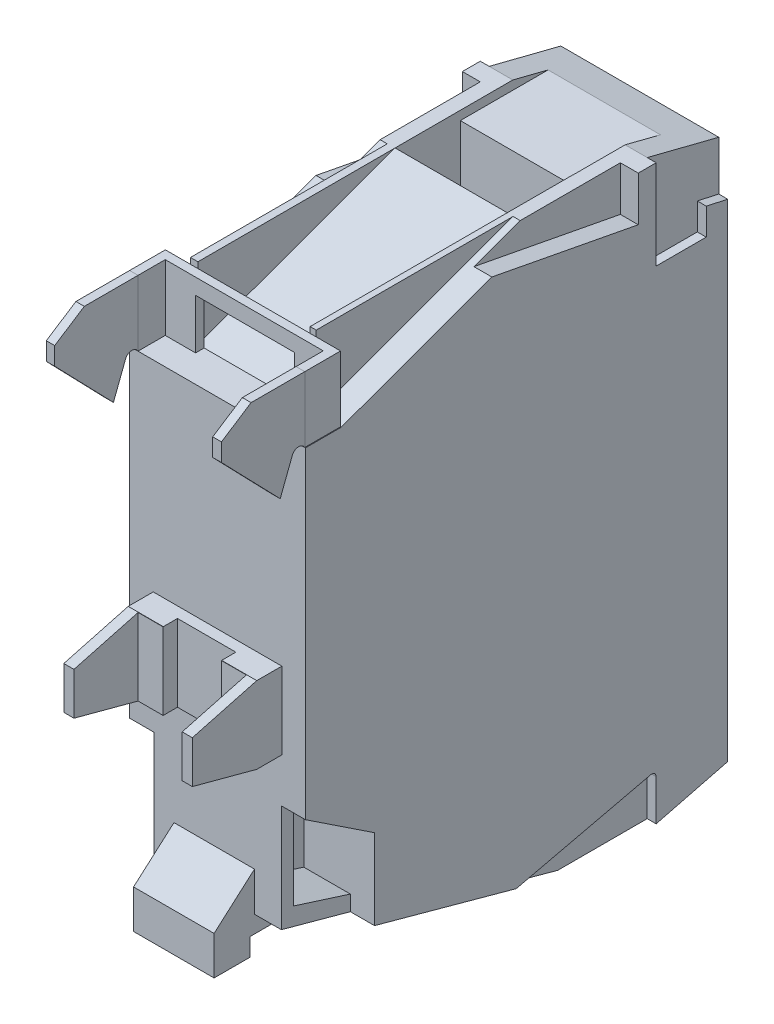
SolidWorks part; units mm, degrees
ref_plane "Front Plane" through (0, 0, 0) normal (0, 0, 1) x (1, 0, 0)
ref_plane "Top Plane" through (0, 0, 0) normal (0, 1, 0) x (1, 0, 0)
ref_plane "Right Plane" through (0, 0, 0) normal (1, 0, 0) x (0, 0, -1)
sketch "Sketch1" plane through (0, 0, 0) normal (0, 0, 1) x (1, 0, 0)
  line L0 (-4.915, -16) -> (4.915, 16) construction
  line L1 (-4.915, 16) -> (4.915, 16)
  line L2 (-4.915, 16) -> (-4.915, -16)
  line L3 (-4.915, -16) -> (4.915, -16)
  line L4 (4.915, 16) -> (4.915, -16)
  line L5 (0, 16) -> (0, -16) construction
  point P4 (0, 0)
  dimension "D1" = 9.83
  dimension "D2" = 32
extrude "Boss-Extrude1" add sketch "Sketch1" along normal blind 23.6
sketch "Sketch2" plane through (4.915, 0, 0) normal (1, 0, 0) x (0, 0, -1)
  line L0 (0, 14.9858) -> (-4, 14.9858) construction
  line L1 (0, -16) -> (0, 16) construction
  line L2 (-4, 16) -> (-4, 15) construction
  line L3 (-23.6, 16) -> (0, 16) construction
  line L4 (-4, 16) -> (0, 14.9858)
  line L5 (-4, 16) -> (0, 16)
  line L6 (0, 16) -> (0, 14.9858)
  line L7 (-23.6, 0) -> (0, 0) construction
  line L8 (-23.6, -16) -> (-23.6, 16) construction
  line L9 (-4, -16) -> (-4, -15) construction
  line L10 (0, -14.9858) -> (-4, -14.9858) construction
  line L11 (0, -16) -> (0, -14.9858)
  line L12 (-4, -16) -> (0, -16)
  line L13 (-4, -16) -> (0, -14.9858)
extrude "Cut-Extrude1" cut sketch "Sketch2" against normal up to next
sketch "Sketch3" plane through (4.915, 0, 0) normal (1, 0, 0) x (0, 0, -1)
  line L0 (-4, 16) -> (-4, 11)
  line L1 (-4, 11) -> (-1.2, 11)
  line L2 (-1.2, 11) -> (-1.2, 12.5)
  line L3 (-1.2, 12.5) -> (0, 12.2359)
  line L4 (0, -14.9858) -> (0, 14.9858) construction
  line L5 (0, 12.2359) -> (0, 14.9858)
  line L6 (0, 14.9858) -> (-4, 16)
sketch "Sketch5" plane through (-4.915, 0, 0) normal (-1, 0, 0) x (0, 0, 1)
  line L0 (4, 16) -> (4, 11)
  line L1 (4, 11) -> (1.2, 11)
  line L2 (1.2, 11) -> (1.2, 12.5)
  line L3 (1.2, 12.5) -> (0, 12.2359)
  line L4 (0, 12.2359) -> (0, 14.9858)
  line L5 (0, 14.9858) -> (4, 16)
extrude "Cut-Extrude2" cut sketch "Sketch5" against normal blind 0.5
extrude "Cut-Extrude3" cut sketch "Sketch3" against normal blind 0.5
sketch "Sketch6" plane through (4.915, 0, 0) normal (1, 0, 0) x (0, 0, -1)
  line L0 (-4, -16) -> (-9, -16) construction
  line L1 (-23.6, -16) -> (-4, -16) construction
  line L2 (-23.6, 16) -> (-23.6, -12) construction
  line L3 (-23.6, -16) -> (-23.6, 16) construction
  line L4 (-23.6, -12) -> (-9, -16)
  line L5 (-9, -16) -> (-23.6, -16)
  line L6 (-23.6, -16) -> (-23.6, -12)
extrude "Cut-Extrude4" cut sketch "Sketch6" against normal up to next
sketch "Sketch7" plane through (4.915, 0, 0) normal (1, 0, 0) x (0, 0, -1)
  line L0 (-23.6, 2) -> (0, 2) construction
  line L1 (-23.6, -12) -> (-23.6, 16) construction
  line L2 (0, -14.9858) -> (0, 12.2359) construction
  line L3 (-4, -16) -> (-4, -13.7152)
  line L4 (-4.3069, -13.4717) -> (-11.8196, -15.2275)
  line L5 (-9, -16) -> (-23.6, -12) construction
  line L6 (-11.8196, -15.2275) -> (-9, -16)
  line L7 (-9, -16) -> (-4, -16)
  arc A0 (-4, -13.7152) -> (-4.3069, -13.4717) centre (-4.25, -13.7152) ccw
  dimension "D1" = 0.25
extrude "Cut-Extrude5" cut sketch "Sketch7" against normal blind 0.5
sketch "Sketch8" plane through (-4.915, 0, 0) normal (-1, 0, 0) x (0, 0, 1)
  line L0 (4, -16) -> (4, -13.7152)
  line L1 (4, -13.7152) -> (4.0946, -13.5193)
  line L2 (4.0946, -13.5193) -> (4.3069, -13.4717)
  line L3 (4.3069, -13.4717) -> (11.8196, -15.2275)
  line L4 (11.8196, -15.2275) -> (9, -16)
  line L5 (9, -16) -> (4, -16)
  arc A0 (4.3069, -13.4717) -> (4, -13.7152) centre (4.25, -13.7152) ccw construction
extrude "Cut-Extrude6" cut sketch "Sketch8" against normal blind 0.5 contours L5 L0 L1 L2 L3 L4
sketch "Sketch9" plane through (4.915, 0, 0) normal (1, 0, 0) x (0, 0, -1)
  line L1 (-23.6, 16) -> (-21.6, 16)
  line L2 (-23.6, 16) -> (-23.6, 12)
  line L3 (-23.6, 12) -> (-21.6, 12)
  line L4 (-21.6, 16) -> (-21.6, 12)
extrude "Cut-Extrude7" cut sketch "Sketch9" against normal up to next
sketch "Sketch10" plane through (4.915, 0, 0) normal (1, 0, 0) x (0, 0, -1)
  line L0 (-5, 13.5) -> (-4, 13.5) construction
  line L1 (-4, 16) -> (-4, 11) construction
  line L2 (-5, 13.5) -> (-5, 16)
  line L3 (-21.6, 16) -> (-4, 16) construction
  line L4 (-5, 13.5) -> (-18.1024, 16)
  line L5 (-18.1024, 16) -> (-5, 16)
extrude "Cut-Extrude8" cut sketch "Sketch10" against normal blind 1
sketch "Sketch11" plane through (4.915, 0, 0) normal (1, 0, 0) x (0, 0, -1)
  line L0 (-21.6, 16) -> (-10.6, 16)
  line L1 (-10.6, 16) -> (-21.6, 12)
  line L2 (-21.6, 12) -> (-21.6, 16)
extrude "Cut-Extrude9" cut sketch "Sketch11" against normal blind 1.4
sketch "Sketch12" plane through (-4.915, 0, 0) normal (-1, 0, 0) x (0, 0, 1)
  line L0 (5, 16) -> (5, 13.5)
  line L1 (5, 13.5) -> (18.1024, 16)
  line L2 (18.1024, 16) -> (5, 16)
extrude "Cut-Extrude10" cut sketch "Sketch12" against normal blind 1 contours L2 L0 L1
sketch "Sketch13" plane through (-4.915, 0, 0) normal (-1, 0, 0) x (0, 0, 1)
  line L0 (21.6, 12) -> (21.6, 16)
  line L1 (21.6, 16) -> (10.6, 16)
  line L2 (10.6, 16) -> (21.6, 12)
extrude "Cut-Extrude11" cut sketch "Sketch13" against normal blind 1.4
sketch "Sketch14" plane through (4.915, 0, 0) normal (1, 0, 0) x (0, 0, -1)
  line L0 (-23.6, -12) -> (-23.6, -6)
  line L1 (-23.6, -12) -> (-23.6, 12) construction
  line L2 (-23.6, -12) -> (-19.7422, -13.0569)
  line L3 (-11.8196, -15.2275) -> (-23.6, -12) construction
  line L4 (-19.7422, -13.0569) -> (-19.7422, -8.5569)
  line L5 (-19.7422, -8.5569) -> (-23.6, -6)
extrude "Cut-Extrude12" cut sketch "Sketch14" against normal blind 1.35
sketch "Sketch15" plane through (-4.915, 0, 0) normal (-1, 0, 0) x (0, 0, 1)
  line L0 (19.7422, -13.0569) -> (19.7422, -8.5569)
  line L1 (19.7422, -8.5569) -> (23.6, -6)
  line L2 (23.6, -6) -> (23.6, -12)
  line L3 (23.6, -12) -> (19.7422, -13.0569)
extrude "Cut-Extrude13" cut sketch "Sketch15" against normal blind 1.35
sketch "Sketch16" plane through (3.565, 0, 0) normal (1, 0, 0) x (0, 0, -1)
  line L0 (-22.9226, -6.449) -> (-22.9226, -11.1904)
  line L1 (-19.7422, -8.5569) -> (-23.6, -6) construction
  line L2 (-22.9226, -11.1904) -> (-19.7422, -12.2011)
  line L3 (-19.7422, -13.0569) -> (-19.7422, -8.5569) construction
  line L4 (-22.9226, -6.449) -> (-19.7422, -8.5569)
  line L5 (-19.7422, -8.5569) -> (-19.7422, -12.2011)
extrude "Cut-Extrude14" cut sketch "Sketch16" against normal blind 2.6
sketch "Sketch18" plane through (-3.565, 0, 0) normal (-1, 0, 0) x (0, 0, 1)
  line L0 (19.7422, -12.2011) -> (19.7422, -8.5569)
  line L1 (19.7422, -8.5569) -> (22.9226, -6.449)
  line L2 (22.9226, -6.449) -> (22.9226, -11.1904)
  line L3 (22.9226, -11.1904) -> (19.7422, -12.2011)
extrude "Cut-Extrude15" cut sketch "Sketch18" against normal blind 3.6
sketch "Sketch19" plane through (0, -14.0807, -3.5701) normal (0, -0.9693, -0.2458) x (1, 0, 0)
  line L1 (3.7246, 7.1036) -> (-3.4583, 7.1036)
  line L2 (3.7246, 7.1036) -> (3.7246, 4.9248)
  line L3 (3.7246, 4.9248) -> (-3.4583, 4.9248)
  line L4 (-3.4583, 7.1036) -> (-3.4583, 4.9248)
extrude "Cut-Extrude18" cut sketch "Sketch19" against normal blind 1.32
chamfer "Chamfer2" distance 0.75 angle 75 3 edges at (-3.4583, -15.5588, 2.2597) (0.1332, -15.291, 1.2037) (3.7246, -15.5588, 2.2597)
sketch "Sketch21" plane through (0, -14.0807, -3.5701) normal (0, -0.9693, -0.2458) x (-1, 0, 0)
  line L1 (-4.0773, -7.1036) -> (4.2083, -7.1036)
  line L2 (-4.0773, -7.1036) -> (-4.0773, -12.5673)
  line L3 (-4.0773, -12.5673) -> (4.2083, -12.5673)
  line L4 (4.2083, -7.1036) -> (4.2083, -12.5673)
extrude "Cut-Extrude19" cut sketch "Sketch21" against normal blind 4.25
sketch3d "3DSketch1" plane through (0, 0, 0) normal (0, 0, 1) x (1, 0, 0)
  dimension "D1" = 3.75
sketch "Sketch22" plane through (-0.185, 0, 0) normal (1, 0, 0) x (0, 0, -1)
  line L0 (-19.8581, -12.9572) -> (-23.8581, -12.9572)
  line L1 (-23.8581, -12.9572) -> (-23.8581, -13.9572)
  line L2 (-23.8581, -13.9572) -> (-25.8581, -13.9572)
  line L3 (-25.8581, -13.9572) -> (-25.8581, -11.7988)
  line L4 (-25.8581, -11.7988) -> (-23.5927, -9.8081)
  line L5 (-23.5927, -9.8081) -> (-23.4731, -11.3744)
  line L6 (-23.4731, -11.3744) -> (-19.8581, -12.9572)
extrude "Boss-Extrude2" add sketch "Sketch22" against normal blind 2.25 and the other way blind 2.25
sketch "Sketch23" plane through (0, 16, 0) normal (0, 1, 0) x (1, 0, 0)
  line L1 (-3.0982, -6.933) -> (3.1743, -6.933)
  line L2 (-3.0982, -6.933) -> (-3.0982, -21.6)
  line L3 (-3.0982, -21.6) -> (3.1743, -21.6)
  line L4 (3.1743, -6.933) -> (3.1743, -21.6)
  line L5 (-3.515, -21.6) -> (3.515, -21.6) construction
extrude "Cut-Extrude20" cut sketch "Sketch23" against normal up to vertex (4 mm away)
sketch "Sketch24" plane through (3.1743, 0, 0) normal (-1, 0, 0) x (0, 0, 1)
  line L0 (10.5797, 16) -> (21.6, 12)
  line L1 (21.6, 16) -> (6.933, 16) construction
  line L2 (21.6, 12) -> (10.5797, 12)
  line L3 (21.6, 12) -> (6.933, 12) construction
  line L4 (10.5797, 12) -> (10.5797, 16)
extrude "Boss-Extrude3" add sketch "Sketch24" along normal up to next
sketch "Sketch25" plane through (0, 16, 0) normal (0, 1, 0) x (1, 0, 0)
  line L1 (-3.0982, -6.933) -> (3.1814, -6.933)
  line L2 (-3.0982, -6.933) -> (-3.0982, -0.7769)
  line L3 (-3.0982, -0.7769) -> (3.1814, -0.7769)
  line L4 (3.1814, -6.933) -> (3.1814, -0.7769)
extrude "Cut-Extrude21" cut sketch "Sketch25" against normal blind 0.5
sketch "Sketch26" plane through (0, 0, 0) normal (0, 0, -1) x (-1, 0, 0)
  line L0 (-4.915, -1.375) -> (4.915, -1.375) construction
  line L3 (-3.5929, -3.5227) -> (3.5929, 0.7728) construction
  line L4 (-3.5929, 0.7728) -> (3.5929, 0.7728)
  line L5 (-3.5929, 0.7728) -> (-3.5929, -3.5227)
  line L6 (-3.5929, -3.5227) -> (3.5929, -3.5227)
  line L7 (3.5929, 0.7728) -> (3.5929, -3.5227)
  line L8 (4.915, 12.2359) -> (4.915, -14.9858) construction
  line L9 (-4.915, -14.9858) -> (-4.915, 12.2359) construction
  point P10 (0, -1.375)
  point P11 (0, -1.375)
  dimension "D1" = 7.1858
extrude "Cut-Extrude22" cut sketch "Sketch26" against normal through all
sketch "Sketch27" plane through (0, 0, 23.6) normal (0, 0, 1) x (1, 0, 0)
  line L1 (-3.5929, 0.7728) -> (3.5929, 0.7728)
  line L2 (-3.5929, 0.7728) -> (-3.5929, -3.5227)
  line L3 (-3.5929, -3.5227) -> (3.5929, -3.5227)
  line L4 (3.5929, 0.7728) -> (3.5929, -3.5227)
extrude "Boss-Extrude4" add sketch "Sketch27" along normal blind 5 and the other way blind 19.5 separate body
sketch "Sketch28" plane through (0, 0.7728, 0) normal (0, 1, 0) x (1, 0, 0)
  line L0 (3.0249, -28.6) -> (3.0249, -25.0138)
  line L1 (3.5929, -28.6) -> (-3.5929, -28.6) construction
  line L2 (3.0249, -25.0138) -> (1.6314, -25.0138)
  line L3 (1.6314, -25.0138) -> (1.6314, -24.2085)
  line L4 (1.6314, -24.2085) -> (-1.6314, -24.2085)
  line L5 (0, -24.2085) -> (0, -23.6)
  line L6 (3.5929, -23.6) -> (-3.5929, -23.6) construction
  line L7 (-3.5929, -23.6) -> (3.5929, -23.6)
  line L8 (3.5929, -23.6) -> (3.5929, -28.6)
  line L9 (3.5929, -28.6) -> (3.0249, -28.6)
  line L10 (0, -23.6) -> (0, -28.6) construction
  line L11 (-3.5929, -28.6) -> (-3.0249, -28.6)
  line L12 (-3.5929, -23.6) -> (-3.5929, -28.6)
  line L13 (-1.6314, -25.0138) -> (-1.6314, -24.2085)
  line L14 (-3.0249, -25.0138) -> (-1.6314, -25.0138)
  line L15 (-3.0249, -28.6) -> (-3.0249, -25.0138)
  line M11 (-3.5929, -28.6) -> (3.5929, -28.6)
extrude "Cut-Extrude23" cut sketch "Sketch28" against normal up to next (4.2956 mm away) contours L10 L4 L13 L14 L15 M11 | L4 L10 L0 L2 L3 M11
chamfer "Chamfer3" distance 3.6 angle 15 2 edges at (3.3089, 0.7728, 28.6) (3.3089, -3.5227, 28.6)
chamfer "Chamfer4" distance 3.6 angle 15 2 edges at (-3.3089, 0.7728, 28.6) (-3.3089, -3.5227, 28.6)
sketch "Sketch29" plane through (0, 0, 4.1) normal (0, 0, -1) x (-1, 0, 0)
  line L0 (3.5929, -3.5227) -> (-3.5929, -3.5227) construction
  line L1 (-1.7574, 0.6607) -> (1.7416, 0.6607)
  line L2 (-1.7574, 0.6607) -> (-1.7574, -3.5227)
  line L3 (-1.7574, -3.5227) -> (1.7416, -3.5227)
  line L4 (1.7416, 0.6607) -> (1.7416, -3.5227)
extrude "Boss-Extrude5" add sketch "Sketch29" along normal blind 0.25
sketch "Sketch30" plane through (0, 0, 0) normal (0, 0, -1) x (-1, 0, 0)
  line L1 (-4.3873, 11.3819) -> (4.2265, 11.3819)
  line L2 (-4.3873, 11.3819) -> (-4.3873, 7.8691)
  line L3 (-4.3873, 7.8691) -> (4.2265, 7.8691)
  line L4 (4.2265, 11.3819) -> (4.2265, 7.8691)
  circle A0 centre (0, 9.6814) radius 2.75
  circle A1 centre (0, -10.2363) radius 2.75
extrude "Cut-Extrude24" cut sketch "Sketch30" against normal blind 4 contours A0 L3 L4 L1 | L1 A0 L3 | L1 A0 | A1
sketch "Sketch31" plane through (0, 0, 4) normal (0, 0, -1) x (-1, 0, 0)
  line L0 (0, 12.4314) -> (0, 6.9314) construction
  line L1 (0, -10.2363) -> (0, -7.4863) construction
  arc A1 (2.1613, 11.3819) -> (-2.1613, 11.3819) centre (0, 9.6814) ccw construction
  arc A2 (-2.0683, 7.8691) -> (2.0683, 7.8691) centre (0, 9.6814) ccw construction
  circle A3 centre (0, -10.2363) radius 2.75 construction
  circle A4 centre (0, 9.6814) radius 2.75
  circle A5 centre (0, -10.2363) radius 2.75
extrude "Cut-Extrude25" cut sketch "Sketch31" against normal blind 1
sketch "Sketch32" plane through (0, 0, 5) normal (0, 0, -1) x (-1, 0, 0)
  line L0 (0, 12.4314) -> (0, 9.6814) construction
  line L1 (0, 9.6814) -> (0, -7.4863) construction
  line L2 (0, -7.4863) -> (0, -10.2363) construction
  circle A0 centre (0, 9.6814) radius 2.75 construction
  arc A1 (2.2128, -11.8691) -> (-2.2128, -11.8691) centre (0, -10.2363) ccw construction
  circle A2 centre (0, 9.6814) radius 2.75
  circle A3 centre (0, -10.2363) radius 2.75
extrude "Boss-Extrude6" add sketch "Sketch32" along normal blind 0.75 separate body
sketch "Sketch33" plane through (0, 0, 4.25) normal (0, 0, -1) x (-1, 0, 0)
  line L0 (0, 9.6814) -> (0, -10.2363) construction
  line L1 (0, -0.2774) -> (-5.7173, -0.2774) construction
  line L2 (-1.4585, 9.3898) -> (1.4585, 9.9731) construction
  line L3 (-0.3233, 11.8782) -> (0.299, 11.8782)
  line L4 (-0.3233, 11.8782) -> (-0.3233, 7.392)
  line L5 (-0.3233, 7.392) -> (0.299, 7.392)
  line L6 (0.299, 11.8782) -> (0.299, 7.392)
  line L7 (-1.4585, 9.9731) -> (1.4585, 9.9731)
  line L8 (-1.4585, 9.9731) -> (-1.4585, 9.3898)
  line L9 (-1.4585, 9.3898) -> (1.4585, 9.3898)
  line L10 (1.4585, 9.9731) -> (1.4585, 9.3898)
  line L11 (-1.4585, -9.9447) -> (1.4585, -10.5279) construction
  line L12 (1.4585, -10.5279) -> (1.4585, -9.9447)
  line L13 (-1.4585, -9.9447) -> (1.4585, -9.9447)
  line L14 (-1.4585, -10.5279) -> (-1.4585, -9.9447)
  line L15 (-1.4585, -10.5279) -> (1.4585, -10.5279)
  line L16 (0.299, -12.4331) -> (0.299, -7.9469)
  line L17 (-0.3233, -7.9469) -> (0.299, -7.9469)
  line L18 (-0.3233, -12.4331) -> (-0.3233, -7.9469)
  line L19 (-0.3233, -12.4331) -> (0.299, -12.4331)
  point P11 (0, 9.6814)
  circle M7 centre (0, 9.6814) radius 2.75
extrude "Cut-Extrude26" cut sketch "Sketch33" against normal blind 0.75 contours L4 L7 L6 L3 | L10 L7 L6 L9 | L9 L4 L5 L6 M7 | L4 L9 L6 L7 | L8 L9 L4 L7 | L18 L13 L16 L17 | L18 L15 L16 L13 | L18 L19 L16 L15
sketch "Sketch35" plane through (0, 0, 21.6) normal (0, 0, 1) x (1, 0, 0)
  line L1 (-4.915, 12) -> (4.8761, 12)
  line L2 (-4.915, 12) -> (-4.915, 15.6698)
  line L3 (-4.915, 15.6698) -> (4.8761, 15.6698)
  line L4 (4.8761, 12) -> (4.8761, 15.6698)
extrude "Boss-Extrude8" add sketch "Sketch35" along normal up to vertex (2 mm away) separate body
sketch "Sketch37" plane through (-4.915, 0, 0) normal (-1, 0, 0) x (0, 0, 1)
  line L0 (23.6, 15.6698) -> (26.6, 15.6698)
  line L1 (26.6, 15.6698) -> (28.2571, 14.5987)
  line L2 (28.2571, 14.5987) -> (28.2571, 13.5987)
  line L3 (28.2571, 13.5987) -> (24.9738, 10.2049)
  line L4 (24.9738, 10.2049) -> (24.2822, 12.0004)
  line L5 (23.6, 15.6698) -> (23.6, 12)
  arc A0 (24.2822, 12.0004) -> (23.6, 12) centre (23.9412, 11.8237) ccw
extrude "Boss-Extrude9" add sketch "Sketch37" against normal up to vertex (9.7911 mm away) separate body
sketch "Sketch38" plane through (0, 15.6698, 0) normal (0, 1, 0) x (1, 0, 0)
  line L1 (-4.4453, -22.0771) -> (4.3869, -22.0771)
  line L2 (-4.4453, -22.0771) -> (-4.4453, -30.1169)
  line L3 (-4.4453, -30.1169) -> (4.3869, -30.1169)
  line L4 (4.3869, -22.0771) -> (4.3869, -30.1169)
extrude "Cut-Extrude32" cut sketch "Sketch38" against normal up to vertex (3.6698 mm away)
sketch "Sketch41" plane through (0, 12, 0) normal (0, 1, 0) x (1, 0, 0)
  line L1 (-4.4453, -24.2823) -> (4.3869, -24.2823)
  line L2 (-4.4453, -24.2823) -> (-4.4453, -26.7105)
  line L3 (-4.4453, -26.7105) -> (4.3869, -26.7105)
  line L4 (4.3869, -24.2823) -> (4.3869, -26.7105)
extrude "Cut-Extrude33" cut sketch "Sketch41" against normal up to next
sketch "Sketch42" plane through (0, 0, 22.0771) normal (0, 0, 1) x (1, 0, 0)
  line L0 (4.3869, 12) -> (-4.4453, 12) construction
  line L1 (-2.7506, 12) -> (2.7661, 12)
  line L2 (-2.7506, 12) -> (-2.7506, 14.7886)
  line L3 (-2.7506, 14.7886) -> (2.7661, 14.7886)
  line L4 (2.7661, 12) -> (2.7661, 14.7886)
extrude "Cut-Extrude34" cut sketch "Sketch42" against normal up to next
sketch "Sketch43" plane through (0, 0, 0) normal (0, 0, -1) x (-1, 0, 0)
  text T0 "NC" font "Century Gothic" height in points 8
  text T1 "1"
  text T2 "2"
extrude "Cut-Extrude35" cut sketch "Sketch43" against normal blind 0.01
